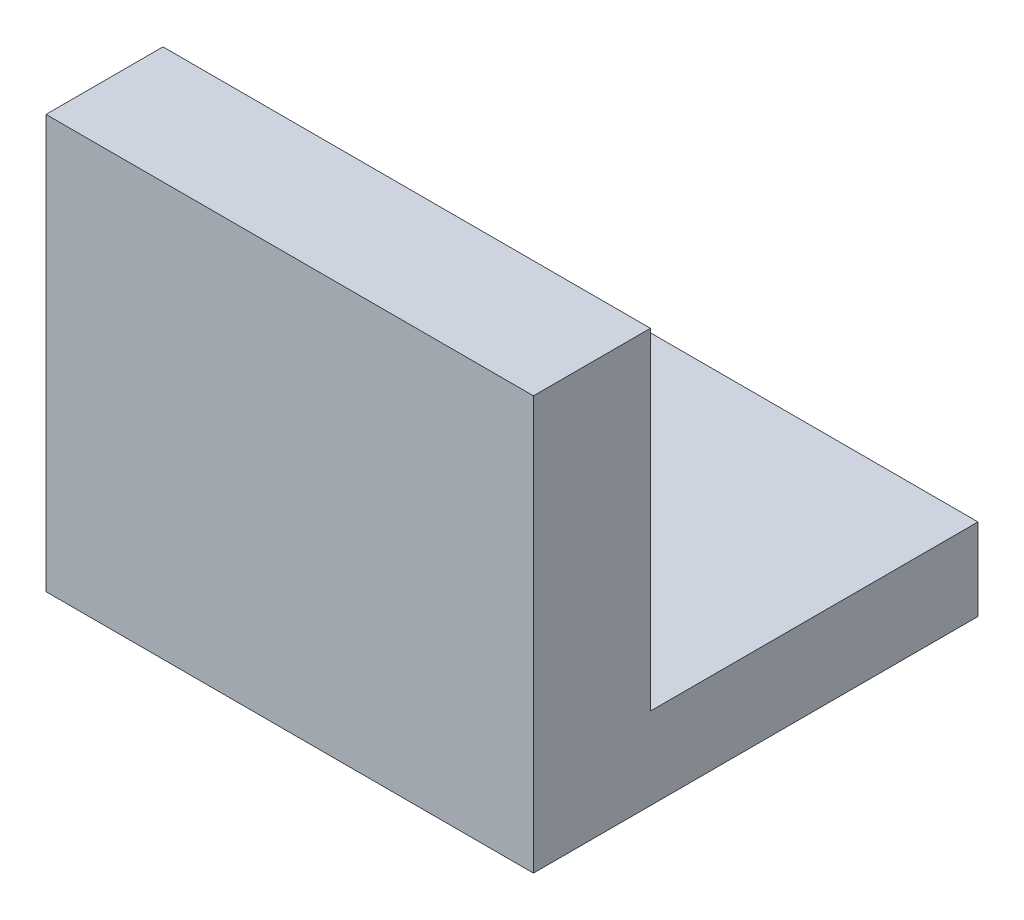
SolidWorks part; units mm, degrees
ref_plane "Plan de face" through (0, 0, 0) normal (0, 0, 1) x (1, 0, 0)
ref_plane "Plan de dessus" through (0, 0, 0) normal (0, 1, 0) x (1, 0, 0)
ref_plane "Plan de droite" through (0, 0, 0) normal (1, 0, 0) x (0, 0, -1)
sketch "Esquisse1" plane through (0, 0, 0) normal (0, 0, 1) x (1, 0, 0)
  line L1 (0, 0) -> (12.5, 0)
  line L2 (0, 0) -> (0, 2.1)
  line L3 (0, 2.1) -> (12.5, 2.1)
  line L4 (12.5, 0) -> (12.5, 2.1)
  dimension "D1" = 12.5
  dimension "D2" = 2.1
extrude "Boss.-Extru.1" add sketch "Esquisse1" along normal blind 8.4
sketch "Esquisse2" plane through (0, 0, 8.4) normal (0, 0, 1) x (1, 0, 0)
  line L1 (12.5, 0) -> (0, 0)
  line L2 (12.5, 0) -> (12.5, 10.6002)
  line L3 (12.5, 10.6002) -> (0, 10.6002)
  line L4 (0, 0) -> (0, 10.6002)
extrude "Boss.-Extru.2" add sketch "Esquisse2" along normal blind 3
